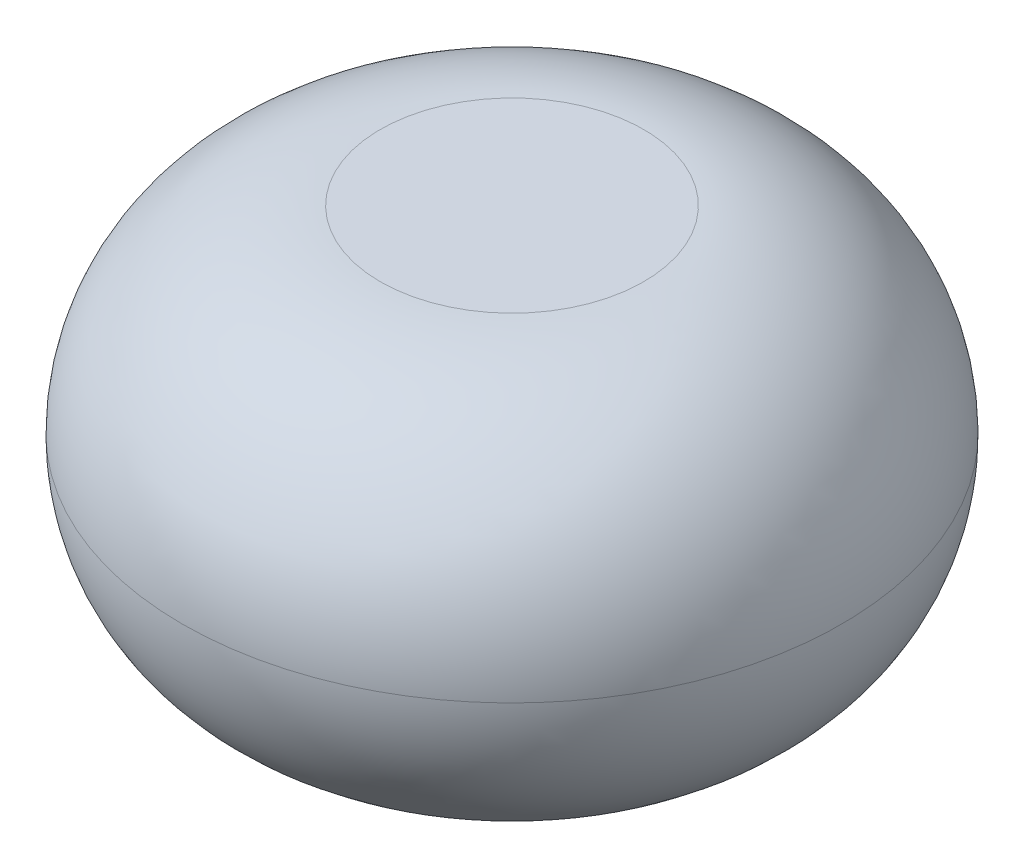
SolidWorks part; units mm, degrees
ref_plane "Front Plane" through (0, 0, 0) normal (0, 0, 1) x (1, 0, 0)
ref_plane "Top Plane" through (0, 0, 0) normal (0, 1, 0) x (1, 0, 0)
ref_plane "Right Plane" through (0, 0, 0) normal (1, 0, 0) x (0, 0, -1)
sketch "Sketch2" plane through (0, 0, 0) normal (0, 1, 0) x (1, 0, 0)
  circle A0 centre (0, 0) radius 125
  dimension "D1" = 250
extrude "Boss-Extrude1" add sketch "Sketch2" along normal blind 150
fillet "Fillet2" radius 75 2 edges at (0, 0, 125) (0, 150, 125)
